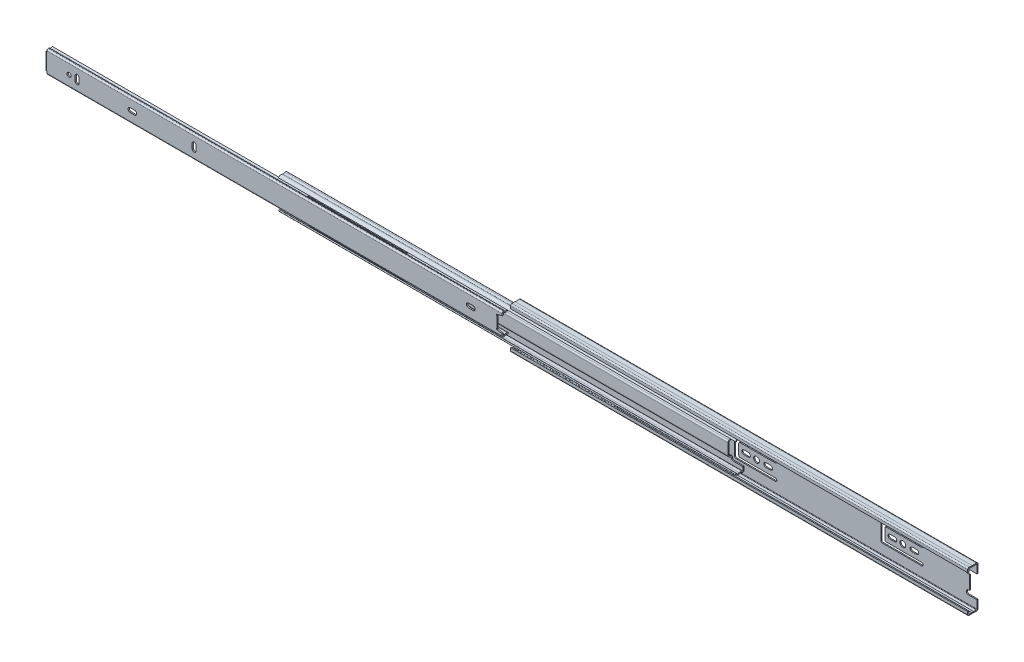
SolidWorks part; units mm, degrees
ref_plane "Front" through (0, 0, 0) normal (0, 0, 1) x (1, 0, 0)
ref_plane "Top" through (0, 0, 0) normal (0, 1, 0) x (1, 0, 0)
ref_plane "Right" through (0, 0, 0) normal (1, 0, 0) x (0, 0, -1)
sketch "Sketch1" plane through (0, 0, 0) normal (1, 0, 0) x (0, 0, -1)
  line L1 (5.6388, 0) -> (-5.6388, 0) construction
  line L4 (-4.1393, 22.8203) -> (-0.7433, 22.6989)
  line L5 (-1.1312, 21.5182) -> (-4.1819, 21.6273)
  line L6 (-4.445, 18.415) -> (-5.6388, 18.415)
  line L7 (-4.445, 21.3734) -> (-4.445, 18.415)
  line L8 (-5.6388, 18.415) -> (-5.6388, 21.3734)
  line L9 (3.9237, 21.6269) -> (0.7619, 21.5441)
  line L10 (5.6388, 0) -> (5.6388, 21.1191)
  line L11 (4.445, 21.1191) -> (4.445, 0)
  line L12 (5.6388, 0) -> (4.445, 0)
  line L13 (-0.7433, 22.6989) -> (3.8925, 22.8203)
  arc A0 (-4.445, 21.3734) -> (-4.1819, 21.6273) centre (-4.191, 21.3734) cw
  arc A1 (-5.6388, 21.3734) -> (-4.1393, 22.8203) centre (-4.191, 21.3734) cw
  arc A3 (3.9237, 21.6269) -> (4.445, 21.1191) centre (3.937, 21.1191) cw
  arc A4 (3.8925, 22.8203) -> (5.6388, 21.1191) centre (3.937, 21.1191) cw
  arc A5 (-1.1312, 21.5182) -> (0.7619, 21.5441) centre (-0.1524, 19.1744) cw
  dimension "D2" = 19.1744
  dimension "D7" = 0.254
  dimension "D8" = 0.508
  dimension "D6" = 2.54
  dimension "D9" = 1.1938
  dimension "D10" = 88.5
  dimension "D1" = 11.2776
  dimension "D3" = 5.7912
  dimension "D4" = 36.83
  dimension "D5" = 1.1938
  dimension "D11" = 87.953
  dimension "D12" = 45.6406
extrude "Extrude1" add sketch "Sketch1" along normal mid plane 500.126
ref_plane "Travel / 2" through (-504.063, 0, 0) normal (-1, 0, 0) x (0, 0, 1)
sketch "Sketch2" plane through (-504.063, 0, 0) normal (-1, 0, 0) x (0, 0, 1)
  line L0 (0.0254, 6.1159) -> (0.0254, 0)
  line L2 (-5.6388, 0) -> (5.6388, 0) construction
  line L3 (5.6388, 21.3734) -> (5.6388, 18.415) construction
  line L7 (-4.445, 21.1191) -> (-4.445, 0) construction
  line L8 (-5.6388, 0) -> (-5.6388, 21.1191) construction
  line L13 (-3.5306, 16.3766) -> (-3.5306, 9.5217)
  line L46 (-2.3867, 7.7262) -> (-0.4146, 6.8065)
  arc A0 (0.0254, 6.1159) -> (-0.4146, 6.8065) centre (-0.7366, 6.1159) ccw
  arc A1 (-1.5056, 17.2916) -> (1.2415, 16.9143) centre (0.1524, 19.1744) ccw
  arc A4 (1.1312, 21.5182) -> (-0.7619, 21.5441) centre (0.1524, 19.1744) ccw construction
  arc A19 (-3.5306, 9.5217) -> (-2.3867, 7.7262) centre (-1.5494, 9.5217) ccw
  arc A25 (-1.5056, 17.2916) -> (-3.5306, 16.3766) centre (-2.3114, 16.3766) ccw
  arc A51 (5.7404, 15.6277) -> (1.2415, 16.9143) centre (2.7686, 13.7451) ccw
  dimension "D2" = 8.4074
  dimension "D3" = 27.4903
  dimension "D6" = 1.9812
  dimension "D8" = 12.2319
  dimension "D10" = 2.5088
  dimension "D11" = 1.2192
  dimension "D4" = 0.762
  dimension "D5" = 4.4704
  dimension "D7" = 115
  dimension "D9" = 19.0435
  dimension "D13" = 11.3792
extrude "Middle Member" add sketch "Sketch2" against normal blind 500.126 separate body thin thin type one direction reverse wall 1.2192
ref_plane "Travel" through (-758.063, 0, 0) normal (-1, 0, 0) x (0, 0, 1)
sketch "Sketch3" plane through (-758.063, 0, 0) normal (-1, 0, 0) x (0, 0, 1)
  line L0 (1.2446, 0) -> (0.0254, 0) construction
  line L1 (-5.6388, 0) -> (-5.6388, 21.1191) construction
  line L56 (7.0612, 0) -> (7.0612, 10.6235)
  line L93 (5.5372, 12.1475) -> (5.1643, 12.1475)
  arc A0 (1.2082, 11.9072) -> (4.2365, 11.8325) centre (2.7686, 13.7451) ccw
  arc A29 (7.0612, 10.6235) -> (5.5372, 12.1475) centre (5.5372, 10.6235) ccw
  arc A53 (5.1643, 12.1475) -> (4.2365, 11.8325) centre (5.1643, 10.6235) ccw
  dimension "D1" = 1.524
  dimension "D4" = 1.524
  dimension "D5" = 2.411
  dimension "D2" = 12.7
  dimension "D3" = 12.1475
  dimension "D6" = 5.853
extrude "Drawer Member" add sketch "Sketch3" against normal blind 500.126 thin thin type one direction wall 1.397
sketch "Sketch6" plane through (0, 0, 7.0612) normal (0, 0, 1) x (1, 0, 0)
  line L1 (-758.063, 0) -> (-756.158, 0)
  line L2 (-758.063, 0) -> (-758.063, 12.1475)
  line L3 (-758.063, 12.1475) -> (-756.158, 12.1475)
  line L4 (-756.158, 0) -> (-756.158, 12.1475)
  line L5 (-257.937, 12.1475) -> (-758.063, 12.1475) construction
  line L7 (-758.063, 10.6235) -> (-758.063, 0) construction
  line L8 (-257.937, 0) -> (-758.063, 0) construction
  dimension "D1" = 1.905
extrude "Cut-Extrude1" cut sketch "Sketch6" against normal through all
sketch "Sketch7" plane through (0, 0, 0) normal (0, -1, 0) x (1, 0, 0)
  line L0 (-756.158, 7.0612) -> (-756.412, 7.0612)
  line L1 (-758.063, 5.4102) -> (-758.063, 0.3041)
  line L2 (-758.063, 0.3041) -> (-756.666, 0.3041)
  line L3 (-756.666, 0.3041) -> (-756.666, 5.4102)
  line L4 (-756.412, 5.6642) -> (-756.158, 5.6642)
  line L5 (-257.937, 5.6642) -> (-756.158, 5.6642) construction
  line L6 (-756.158, 7.0612) -> (-756.158, 5.6642)
  line L7 (-257.937, 0.3041) -> (-756.158, 0.3041) construction
  line L9 (-756.158, 5.087) -> (-756.158, 0.3041) construction
  arc A0 (-756.412, 5.6642) -> (-756.666, 5.4102) centre (-756.412, 5.4102) ccw
  arc A1 (-756.412, 7.0612) -> (-758.063, 5.4102) centre (-756.412, 5.4102) ccw
  dimension "D1" = 0.254
  dimension "D2" = 1.905
extrude "Extrude4" add sketch "Sketch7" against normal blind 8.89
sketch "Sketch8" plane through (0, 0, -4.445) normal (0, 0, 1) x (1, 0, 0)
  line L0 (240.4245, 7.6456) -> (241.8588, 7.493)
  line L1 (250.063, 12.2048) -> (240.6664, 12.2048)
  line L2 (241.8588, 7.493) -> (241.8588, 0)
  line L3 (250.063, 0) -> (-250.063, 0) construction
  line L4 (250.063, 21.1191) -> (250.063, 0) construction
  line L5 (250.063, 12.2048) -> (250.063, 0)
  line L6 (250.063, 0) -> (241.8588, 0)
  arc A0 (240.6664, 12.2048) -> (240.4245, 7.6456) centre (240.6664, 9.9188) ccw
  dimension "D3" = 9.9188
  dimension "D1" = 12.2048
  dimension "D2" = 8.2042
  dimension "D4" = 9.3966
  dimension "D5" = 7.493
extrude "Cut-Extrude2" cut sketch "Sketch8" against normal up to next (1.1938 mm away)
sketch "Sketch11" plane through (0, 0, 7.0612) normal (0, 0, 1) x (1, 0, 0)
  line L0 (-263.652, 5.9678) -> (-263.652, 0)
  line L8 (-257.937, 8.5893) -> (-263.7963, 7.2212)
  line L11 (-263.652, 0) -> (-257.937, 0)
  line L12 (-257.937, 0) -> (-257.937, 8.5893)
  arc A1 (-263.7963, 7.2212) -> (-263.652, 5.9678) centre (-263.6519, 6.6028) ccw
  dimension "D3" = 0.635
  dimension "D1" = 5.715
  dimension "D2" = 8.5893
  dimension "D4" = 5.9678
  dimension "D5" = 103.143
extrude "Cut-Extrude3" cut sketch "Sketch11" against normal up to next (1.397 mm away)
sketch "Sketch12" plane through (0, 0, 1.2446) normal (0, 0, 1) x (1, 0, 0)
  line L0 (-3.937, 12.065) -> (-14.097, 12.065)
  line L1 (-3.937, 16.3766) -> (-3.937, 9.5217) construction
  line L2 (-16.637, 9.525) -> (-16.637, 0)
  line L3 (-3.937, 0) -> (-504.063, 0) construction
  line L4 (-16.637, 0) -> (-3.937, 0)
  line L5 (-3.937, 0) -> (-3.937, 12.065)
  arc A0 (-14.097, 12.065) -> (-16.637, 9.525) centre (-14.097, 9.525) ccw
  point P11 (-16.637, 12.065)
  dimension "D3" = 2.54
  dimension "D1" = 12.7
  dimension "D2" = 12.065
extrude "Cut-Extrude4" cut sketch "Sketch12" against normal through all
sketch "Sketch13" plane through (0, 0, -4.445) normal (0, 0, 1) x (1, 0, 0)
  line L0 (-181.6747, 7.112) -> (-206.5032, 7.112)
  line L1 (241.8588, 0) -> (-250.063, 0) construction
  line L2 (-189.7646, 0) -> (-189.7646, 4.2392) construction
  line L3 (-232.6017, 10.287) -> (-181.6747, 10.287)
  line L4 (-250.063, 21.1191) -> (-250.063, 0) construction
  line L5 (-210.3132, 7.112) -> (-232.6017, 7.112)
  line L6 (-209.5512, 0) -> (-209.5512, 6.35)
  line L7 (-207.2652, 6.35) -> (-207.2652, 0)
  line L8 (-187.2881, 2.286) -> (-192.2411, 2.286)
  line L13 (-226.3406, 0) -> (-221.7686, 0)
  line L14 (-218.238, 0) -> (-211.888, 0)
  line L15 (-209.5512, 0) -> (-207.2652, 0)
  line L16 (-204.7506, 0) -> (-200.1786, 0)
  line L17 (-194.5271, 0) -> (-185.0021, 0)
  arc A1 (-232.6017, 10.287) -> (-232.6017, 7.112) centre (-232.6017, 8.6995) ccw
  arc A2 (-209.5512, 6.35) -> (-210.3132, 7.112) centre (-210.3132, 6.35) ccw
  arc A4 (-206.5032, 7.112) -> (-207.2652, 6.35) centre (-206.5032, 6.35) ccw
  arc A7 (-181.6747, 7.112) -> (-181.6747, 10.287) centre (-181.6747, 8.6995) ccw
  arc A8 (-211.888, 0) -> (-218.238, 0) centre (-215.063, 0) ccw
  arc A9 (-221.7686, 0) -> (-226.3406, 0) centre (-224.0546, 0) ccw
  arc A10 (-200.1786, 0) -> (-204.7506, 0) centre (-202.4646, 0) ccw
  arc A11 (-185.0021, 0) -> (-187.2881, 2.286) centre (-187.2881, 0) ccw
  arc A12 (-192.2411, 2.286) -> (-194.5271, 0) centre (-192.2411, 0) ccw
  dimension "D3" = 2.286
  dimension "D4" = 3.175
  dimension "D7" = 8.9916
  dimension "D8" = 21.59
  dimension "D9" = 34.29
  dimension "D10" = 0.762
  dimension "D11" = 17.5387
  dimension "D12" = 9.525
  dimension "D13" = 5.5118
  dimension "D14" = 35
  dimension "D1" = 3.175
  dimension "D2" = 50.927
  dimension "D5" = 2.286
  dimension "D6" = 10.287
extrude "Cut-Extrude5" cut sketch "Sketch13" against normal up to next (1.1938 mm away)
sketch "Sketch32" plane through (0, 0, -5.6388) normal (0, 0, -1) x (-1, 0, 0)
  line L0 (69.6005, 0) -> (79.1255, 0)
  line L1 (83.888, 0) -> (90.238, 0)
  line L2 (93.7305, 0) -> (103.2555, 0)
  line L3 (106.621, 0) -> (111.193, 0)
  line L4 (-241.8588, 0) -> (185.0021, 0) construction
  line L5 (232.6017, 10.287) -> (181.6747, 10.287) construction
  line L6 (181.6747, 7.112) -> (206.5032, 7.112) construction
  line L7 (98.493, 2.286) -> (98.493, -3.4269) construction
  line L8 (74.363, 2.286) -> (74.363, -3.4269) construction
  line L14 (66.4255, 10.287) -> (109.669, 10.287)
  line L15 (105.097, 7.112) -> (66.4255, 7.112)
  line L17 (111.193, 8.763) -> (111.193, 0)
  line L18 (106.621, 0) -> (106.621, 5.588)
  line L23 (71.8865, 2.286) -> (76.8395, 2.286)
  line L25 (96.0165, 2.286) -> (100.9695, 2.286)
  arc A0 (218.238, 0) -> (211.888, 0) centre (215.063, 0) ccw construction
  arc A13 (111.193, 8.763) -> (109.669, 10.287) centre (109.669, 8.763) ccw
  arc A14 (106.621, 5.588) -> (105.097, 7.112) centre (105.097, 5.588) ccw
  arc A17 (66.4255, 10.287) -> (66.4255, 7.112) centre (66.4255, 8.6995) ccw
  arc A20 (79.1255, 0) -> (76.8395, 2.286) centre (76.8395, 0) ccw
  arc A21 (71.8865, 2.286) -> (69.6005, 0) centre (71.8865, 0) ccw
  arc A22 (90.238, 0) -> (83.888, 0) centre (87.063, 0) ccw
  arc A24 (103.2555, 0) -> (100.9695, 2.286) centre (100.9695, 0) ccw
  arc A25 (96.0165, 2.286) -> (93.7305, 0) centre (96.0165, 0) ccw
  dimension "D2" = 1.524
  dimension "D3" = 3.175
  dimension "D4" = 9.525
  dimension "D5" = 2.286
  dimension "D6" = 11.43
  dimension "D7" = 12.7
  dimension "D8" = 24.13
  dimension "D9" = 20.6375
  dimension "D10" = 128
  dimension "D1" = 4.572
extrude "Cut-Extrude14" cut sketch "Sketch32" against normal up to next (1.1938 mm away)
sketch "Sketch33" plane through (83.6094, 0.8125, -5.6388) normal (0, 0, -1) x (-1, 0, 0)
  line L0 (57.2099, -0.8125) -> (66.7349, -0.8125)
  line L1 (71.4974, -0.8125) -> (77.8474, -0.8125)
  line L2 (81.3399, -0.8125) -> (90.8649, -0.8125)
  line L3 (94.2304, -0.8125) -> (98.8024, -0.8125)
  line L7 (86.1024, 1.4735) -> (86.1024, -4.2394) construction
  line L8 (61.9724, 1.4735) -> (61.9724, -3.4269) construction
  line L9 (-158.2494, -0.8125) -> (153.2099, -0.8125) construction
  line L10 (193.2784, 9.4745) -> (150.0349, 9.4745) construction
  line L11 (150.0349, 6.2995) -> (188.7064, 6.2995) construction
  line L14 (54.0349, 9.4745) -> (97.2784, 9.4745)
  line L15 (92.7064, 6.2995) -> (54.0349, 6.2995)
  line L17 (98.8024, 7.9505) -> (98.8024, -0.8125)
  line L18 (94.2304, -0.8125) -> (94.2304, 4.7755)
  line L23 (59.4959, 1.4735) -> (64.4489, 1.4735)
  line L25 (83.6259, 1.4735) -> (88.5789, 1.4735)
  arc A1 (301.8474, -0.8125) -> (295.4974, -0.8125) centre (298.6724, -0.8125) ccw construction
  arc A13 (98.8024, 7.9505) -> (97.2784, 9.4745) centre (97.2784, 7.9505) ccw
  arc A14 (94.2304, 4.7755) -> (92.7064, 6.2995) centre (92.7064, 4.7755) ccw
  arc A17 (54.0349, 9.4745) -> (54.0349, 6.2995) centre (54.0349, 7.887) ccw
  arc A20 (66.7349, -0.8125) -> (64.4489, 1.4735) centre (64.4489, -0.8125) ccw
  arc A21 (59.4959, 1.4735) -> (57.2099, -0.8125) centre (59.4959, -0.8125) ccw
  arc A22 (77.8474, -0.8125) -> (71.4974, -0.8125) centre (74.6724, -0.8125) ccw
  arc A24 (90.8649, -0.8125) -> (88.5789, 1.4735) centre (88.5789, -0.8125) ccw
  arc A25 (83.6259, 1.4735) -> (81.3399, -0.8125) centre (83.6259, -0.8125) ccw
  dimension "D2" = 1.524
  dimension "D3" = 3.175
  dimension "D4" = 9.525
  dimension "D5" = 2.286
  dimension "D6" = 11.43
  dimension "D7" = 12.7
  dimension "D8" = 24.13
  dimension "D9" = 20.6375
  dimension "D10" = 224
  dimension "D1" = 4.572
extrude "Cut-Extrude6" cut sketch "Sketch33" against normal up to next (1.1938 mm away)
sketch "Sketch34" plane through (169.8236, 1.4527, -5.6388) normal (0, 0, -1) x (-1, 0, 0)
  line L0 (-16.6239, -1.4527) -> (-7.0989, -1.4527)
  line L1 (-2.3364, -1.4527) -> (4.0136, -1.4527)
  line L2 (7.5061, -1.4527) -> (17.0311, -1.4527)
  line L3 (20.3966, -1.4527) -> (24.9686, -1.4527)
  line L4 (-72.0352, -1.4527) -> (143.4241, -1.4527) construction
  line L7 (12.2686, 0.8333) -> (12.2686, -4.8796) construction
  line L8 (-11.8614, 0.8333) -> (-11.8614, -4.0671) construction
  line L9 (279.4926, 8.8343) -> (236.2491, 8.8343) construction
  line L10 (236.2491, 5.6593) -> (274.9206, 5.6593) construction
  line L14 (-19.7989, 8.8343) -> (23.4446, 8.8343)
  line L15 (18.8726, 5.6593) -> (-19.7989, 5.6593)
  line L17 (24.9686, 7.3103) -> (24.9686, -1.4527)
  line L18 (20.3966, -1.4527) -> (20.3966, 4.1353)
  line L23 (-14.3379, 0.8333) -> (-9.3849, 0.8333)
  line L25 (9.7921, 0.8333) -> (14.7451, 0.8333)
  arc A0 (388.0616, -1.4527) -> (381.7116, -1.4527) centre (384.8866, -1.4527) ccw construction
  arc A13 (24.9686, 7.3103) -> (23.4446, 8.8343) centre (23.4446, 7.3103) ccw
  arc A14 (20.3966, 4.1353) -> (18.8726, 5.6593) centre (18.8726, 4.1353) ccw
  arc A17 (-19.7989, 8.8343) -> (-19.7989, 5.6593) centre (-19.7989, 7.2468) ccw
  arc A20 (-7.0989, -1.4527) -> (-9.3849, 0.8333) centre (-9.3849, -1.4527) ccw
  arc A21 (-14.3379, 0.8333) -> (-16.6239, -1.4527) centre (-14.3379, -1.4527) ccw
  arc A22 (4.0136, -1.4527) -> (-2.3364, -1.4527) centre (0.8386, -1.4527) ccw
  arc A24 (17.0311, -1.4527) -> (14.7451, 0.8333) centre (14.7451, -1.4527) ccw
  arc A25 (9.7921, 0.8333) -> (7.5061, -1.4527) centre (9.7921, -1.4527) ccw
  dimension "D2" = 1.524
  dimension "D3" = 3.175
  dimension "D4" = 9.525
  dimension "D5" = 2.286
  dimension "D6" = 11.43
  dimension "D7" = 12.7
  dimension "D8" = 24.13
  dimension "D9" = 20.6375
  dimension "D10" = 384.048
  dimension "D1" = 4.572
extrude "Cut E" cut sketch "Sketch34" against normal up to next (1.1938 mm away)
sketch "Sketch24" plane through (0, 0, 7.0612) normal (0, 0, 1) x (1, 0, 0)
  line L0 (-263.652, 0) -> (-756.412, 0) construction
  line L1 (-723.011, 4.826) -> (-723.011, 0) construction
  line L2 (-725.1954, 2.6416) -> (-725.1954, 0)
  line L3 (-725.1954, 0) -> (-720.8266, 0)
  line L4 (-720.8266, 0) -> (-720.8266, 2.6416)
  line L5 (-667.3215, 0) -> (-657.7965, 0)
  line L6 (-665.0355, 2.286) -> (-660.0825, 2.286)
  line L8 (-597.1954, 2.6416) -> (-597.1954, 0)
  line L9 (-597.1954, 0) -> (-592.8266, 0)
  line L10 (-592.8266, 0) -> (-592.8266, 2.6416)
  line L11 (-758.063, 8.89) -> (-758.063, 0) construction
  line L12 (-662.559, 2.286) -> (-662.559, 0) construction
  circle A0 centre (-731.901, 0) radius 2.1844
  arc A1 (-725.1954, 2.6416) -> (-720.8266, 2.6416) centre (-723.011, 2.6416) cw
  arc A2 (-667.3215, 0) -> (-665.0355, 2.286) centre (-665.0355, 0) cw
  arc A3 (-660.0825, 2.286) -> (-657.7965, 0) centre (-660.0825, 0) cw
  arc A4 (-597.1954, 2.6416) -> (-592.8266, 2.6416) centre (-595.011, 2.6416) cw
  dimension "D1" = 4.3688
  dimension "D4" = 8.89
  dimension "D5" = 2.286
  dimension "D7" = 60.452
  dimension "D8" = 128
  dimension "D2" = 35.052
  dimension "D3" = 4.826
  dimension "D6" = 9.525
extrude "Cut-Extrude13" cut sketch "Sketch24" against normal up to next (1.397 mm away)
sketch "Sketch25" plane through (0, 0, 7.0612) normal (0, 0, 1) x (1, 0, 0)
  line L1 (-263.652, 0) -> (-592.8266, 0) construction
  line L5 (-287.4645, 0) -> (-296.9895, 0)
  line L6 (-660.0825, 2.286) -> (-665.0355, 2.286) construction
  line L7 (-294.7035, 2.286) -> (-289.7505, 2.286)
  line L8 (-292.227, 0) -> (-292.227, 2.286) construction
  arc A1 (-720.8266, 2.6416) -> (-725.1954, 2.6416) centre (-723.011, 2.6416) ccw construction
  arc A3 (-294.7035, 2.286) -> (-296.9895, 0) centre (-294.7035, 0) ccw
  arc A4 (-289.7505, 2.286) -> (-287.4645, 0) centre (-289.7505, 0) cw
  arc A5 (-657.7965, 0) -> (-660.0825, 2.286) centre (-660.0825, 0) ccw construction
  dimension "D1" = 430.784
extrude "Cut D" cut sketch "Sketch25" against normal up to next (1.397 mm away)
sketch "Sketch36" plane through (0, 0, 7.0612) normal (0, 0, 1) x (1, 0, 0)
  line L0 (-309.1954, 0) -> (-304.8266, 0)
  line L1 (-304.8266, 0) -> (-304.8266, 2.6416)
  line L2 (-309.1954, 2.6416) -> (-309.1954, 0)
  line L4 (-296.9895, 0) -> (-592.8266, 0) construction
  line L5 (-720.8266, 0) -> (-720.8266, 2.6416) construction
  arc A0 (-304.8266, 2.6416) -> (-309.1954, 2.6416) centre (-307.011, 2.6416) ccw
  circle A1 centre (-319.711, 0) radius 2.1844
  arc A5 (-720.8266, 2.6416) -> (-725.1954, 2.6416) centre (-723.011, 2.6416) ccw construction
  dimension "D1" = 4.3688
  dimension "D2" = 416
  dimension "D3" = 12.7
extrude "Cut B" [suppressed] cut sketch "Sketch36" against normal up to next
sketch "Sketch38" plane through (0, 0, 7.0612) normal (0, 0, 1) x (1, 0, 0)
  line L0 (-501.1954, 0) -> (-501.1954, 2.6416)
  line L1 (-296.9895, 0) -> (-592.8266, 0) construction
  line L2 (-496.8266, 2.6416) -> (-496.8266, 0)
  line L3 (-496.8266, 0) -> (-501.1954, 0)
  line L4 (-720.8266, 0) -> (-720.8266, 2.6416) construction
  line L5 (-492.28, 0) -> (-484.406, 0)
  line L6 (-492.28, 0) -> (-492.28, 2.3749)
  line L7 (-492.28, 2.3749) -> (-484.406, 2.3749)
  line L8 (-484.406, 0) -> (-484.406, 2.3749)
  line L9 (-499.011, 7.182) -> (-499.011, -4.0911) construction
  line L10 (-505.742, 0) -> (-513.616, 0)
  line L11 (-505.742, 0) -> (-505.742, 2.3749)
  line L12 (-505.742, 2.3749) -> (-513.616, 2.3749)
  line L13 (-513.616, 0) -> (-513.616, 2.3749)
  line L14 (-488.343, 2.3749) -> (-488.343, -3.2385) construction
  arc A0 (-501.1954, 2.6416) -> (-496.8266, 2.6416) centre (-499.011, 2.6416) cw
  arc A1 (-720.8266, 2.6416) -> (-725.1954, 2.6416) centre (-723.011, 2.6416) ccw construction
  dimension "D4" = 224
  dimension "D1" = 7.874
  dimension "D2" = 2.3749
  dimension "D3" = 10.668
extrude "Cut A" [suppressed] cut sketch "Sketch38" against normal up to next
ref_plane "Plane3" through (-237.363, 0, 0) normal (-1, 0, 0) x (0, 0, 1)
sketch "Sketch27" plane through (-237.363, 0, 0) normal (-1, 0, 0) x (0, 0, 1)
  line L0 (0.1524, 21.6832) -> (0.1524, 16.6656)
  line L1 (0.1524, 23.635) -> (0.1524, 15.2838) construction
  arc A0 (0.1524, 16.6656) -> (0.1524, 21.6832) centre (0.1524, 19.1744) ccw
  arc A1 (-1.5056, 17.2916) -> (1.2415, 16.9143) centre (0.1524, 19.1744) ccw construction
revolve "Revolve1" add sketch "Sketch27" angle 360 about L1
pattern_linear "LPattern1" count 6 spacing 19.05 along (1, 0, 0) of bodies 128
sketch "Sketch28" plane through (-237.363, 0, 0) normal (-1, 0, 0) x (0, 0, 1)
  line L0 (2.6612, 19.1744) -> (-2.3564, 19.1744) construction
  line L1 (3.9624, 18.7934) -> (-3.6576, 18.7934)
  line L2 (3.9624, 18.7934) -> (3.9624, 19.5554)
  line L3 (3.9624, 19.5554) -> (-3.6576, 19.5554)
  line L4 (-3.6576, 18.7934) -> (-3.6576, 19.5554)
  line L5 (0.1524, 20.5465) -> (0.1524, 17.804) construction
  circle A1 centre (0.1524, 19.1744) radius 2.5088 construction
  point P8 (0.1524, 19.1744)
  dimension "D1" = 7.62
  dimension "D2" = 0.762
extrude "Extrude7" add sketch "Sketch28" along normal blind 6.35 and the other way blind 101.6
ref_plane "Plane4" through (-465.963, 0, 0) normal (-1, 0, 0) x (0, 0, 1)
sketch "Sketch29" plane through (-465.963, 0, 0) normal (-1, 0, 0) x (0, 0, 1)
  line L0 (2.7686, 16.0438) -> (2.7686, 11.4464)
  line L1 (2.7686, 16.6801) -> (2.7686, 10.2973) construction
  arc A0 (2.7686, 11.4464) -> (2.7686, 16.0438) centre (2.7686, 13.7451) ccw
  arc A1 (4.7105, 14.9753) -> (1.7707, 15.816) centre (2.7686, 13.7451) ccw construction
revolve "Revolve2" add sketch "Sketch29" angle 360 about L1
pattern_linear "LPattern2" count 6 spacing 19.05 along (1, 0, 0) of bodies 135
sketch "Sketch30" plane through (-465.963, 0, 0) normal (-1, 0, 0) x (0, 0, 1)
  line L0 (0.4699, 13.7451) -> (5.0673, 13.7451) construction
  line L1 (3.9624, 18.7934) -> (3.9624, 19.5554) construction
  line L2 (0.2286, 14.1261) -> (5.3086, 14.1261)
  line L3 (0.2286, 14.1261) -> (0.2286, 13.3641)
  line L4 (0.2286, 13.3641) -> (5.3086, 13.3641)
  line L5 (5.3086, 14.1261) -> (5.3086, 13.3641)
  line L7 (2.7686, 14.2437) -> (2.7686, 12.7853) construction
  circle A0 centre (2.7686, 13.7451) radius 2.2987 construction
  point P4 (2.7686, 13.7451)
  dimension "D1" = 5.08
extrude "Extrude8" add sketch "Sketch30" along normal blind 6.35 and the other way blind 101.6
mirror "Mirror3" about plane through (0, 0, 0) normal (0, 1, 0) of bodies 126 119 164 117 124 127 159
mirror "Mirror5" about plane through (0, 0, 0) normal (0, 1, 0) of bodies 141 134
ref_plane "Plane5" through (184.1615, 2.286, -5.6388) normal (1, 0, 0) x (0, 0, -1)
ref_plane "Plane6" through (184.1615, 2.286, -4.445) normal (-1, 0, 0) x (0, 0, 1)
sketch "Sketch41" plane through (0, 0, -5.6388) normal (0, 0, 1) x (1, 0, 0)
  line L0 (181.685, 2.286) -> (181.685, -2.286) construction
  line L1 (179.2085, 2.286) -> (184.1615, 2.286) construction
  line L2 (179.2085, -2.286) -> (184.1615, -2.286) construction
  line L3 (186.4475, 0) -> (176.9225, 0) construction
  arc A0 (184.1615, -2.286) -> (184.1615, 2.286) centre (184.1615, 0) ccw construction
  arc A1 (179.2085, 2.286) -> (179.2085, -2.286) centre (179.2085, 0) ccw construction
ref_plane "Plane7" through (-187.2881, -2.286, -5.6388) normal (1, 0, 0) x (0, 0, -1)
ref_plane "Plane8" through (-192.2411, 2.286, -5.6388) normal (1, 0, 0) x (0, 0, -1)
